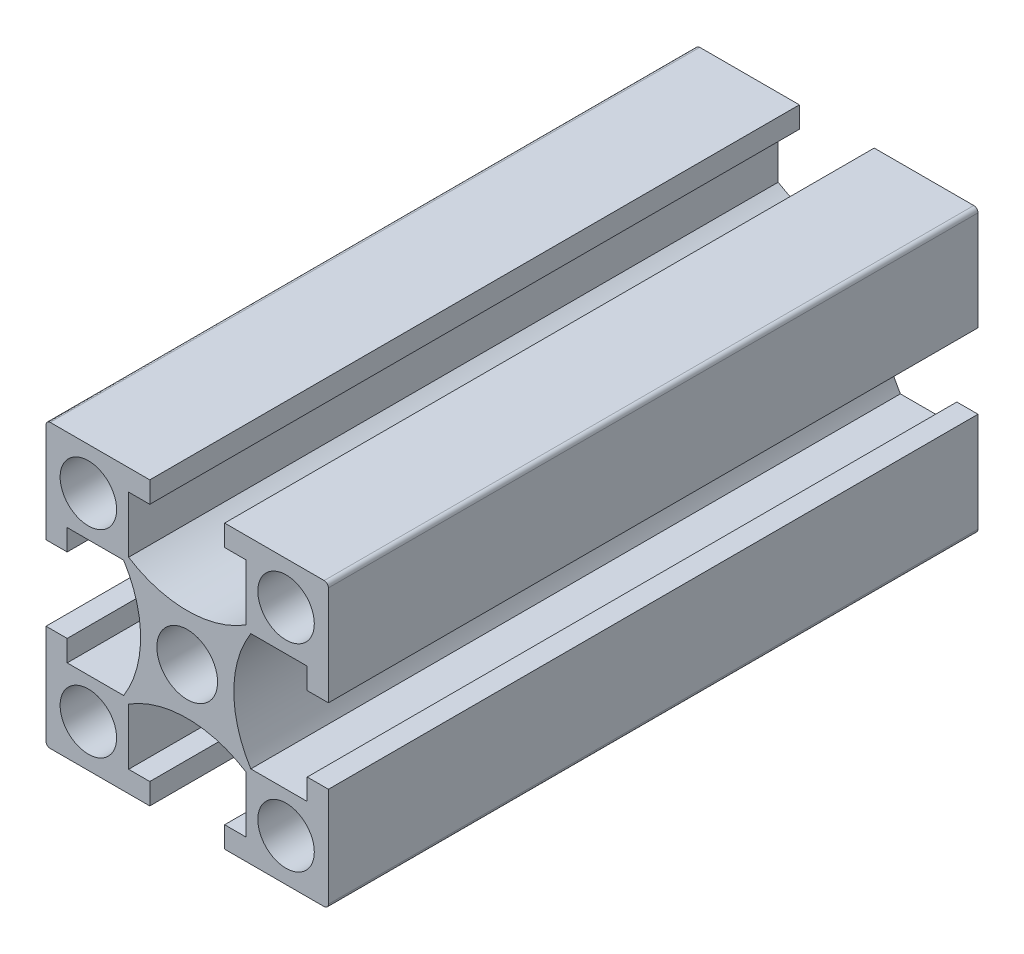
SolidWorks part; units mm, degrees
material "3.0255 (EN-AW 1350A)"
ref_plane "정면" through (0, 0, 0) normal (0, 0, 1) x (1, 0, 0)
ref_plane "윗면" through (0, 0, 0) normal (0, 1, 0) x (1, 0, 0)
ref_plane "우측면" through (0, 0, 0) normal (1, 0, 0) x (0, 0, -1)
sketch "스케치1" plane through (0, 0, 0) normal (0, 0, 1) x (1, 0, 0)
  line L0 (0, 32.0265) -> (0, -31.6588) construction
  line L1 (-10, 10) -> (-10, -10)
  line L2 (-10, 10) -> (10, 10)
  line L3 (-10, 2.65) -> (-8.5, 2.65)
  line L4 (13.6618, 0) -> (-11.6993, 0) construction
  line L5 (-8.5, 2.65) -> (-8.5, 4.15)
  line L6 (-8.5, 4.15) -> (-4.5032, 4.15)
  line L7 (-10, -2.65) -> (-8.5, -2.65)
  line L8 (-8.5, -2.65) -> (-8.5, -4.15)
  line L9 (-8.5, -4.15) -> (-4.5032, -4.15)
  line L10 (-10, -10) -> (10, -10)
  line L11 (10, 10) -> (10, -10)
  circle A0 centre (-7, 7) radius 2
  circle A1 centre (-7, -7) radius 2
  arc A2 (-4.5032, 4.15) -> (-4.5032, -4.15) centre (-11.0587, 0) cw
  circle A3 centre (0, 0) radius 2.15
  circle A4 centre (7, 7) radius 2
  circle A5 centre (7, -7) radius 2
  point P21 (-10, 0)
  point P23 (-3.3, 0)
  point P31 (0, -10)
  point P32 (0, 10)
  dimension "D3" = 4
  dimension "D9" = 6.7
  dimension "D10" = 4.3
  dimension "D11" = 7.7587
  dimension "D1" = 20
  dimension "D2" = 20
  dimension "D4" = 14
  dimension "D5" = 14
  dimension "D6" = 5.3
  dimension "D7" = 8.3
  dimension "D8" = 1.5
extrude "보스-돌출1" add sketch "스케치1" along normal blind 46 contours A0 | A4 | A3 | A5 | A1 | A2 L6 L5 L3 L1 L7 L8 L9 | L2 L11 L10 L1 region at (-6.6069, 0, 0) region at (-7, 7, 0) region at (-7, -7, 0) region at (0, 0, 0) region at (7, 7, 0) region at (7, -7, 0)
extrude "컷-돌출1" cut sketch "스케치1<3>" along normal up to next contours A2 L6 L5 L3 L1 L7 L8 L9 region at (-6.6069, 0, 0)
sketch "스케치1<3>" plane through (0, 0, 0) normal (0, 0, 1) x (1, 0, 0) same geometry as "스케치1"
pattern_circular "원형 패턴1" count 4 over 360 about axis through (0, 0, 46) along (0, 0, -1) of "컷-돌출1" reverse direction yes
fillet "필렛1" radius 0.3 4 edges at (10, -10, 23) (-10, -10, 23) (-10, 10, 23) (10, 10, 23)
sketch "스케치2" plane through (0, 0, 0) normal (1, 0, 0) x (0, 0, -1)
  line L0 (3.7612, 0) -> (-18.9549, 0) construction
  line L1 (-23, 34.3807) -> (-23, -14.9807) construction
  line L4 (0, -4.15) -> (0, 4.15) construction
  line L5 (0, 9.7) -> (-46, 9.7) construction
  line L6 (0, 9.7) -> (-46, 9.7) construction
  circle A0 centre (-8.5, 0) radius 2.5
  point P6 (-23, 9.7)
  dimension "D1" = 5
  dimension "D2" = 8.5
extrude "컷-돌출2" cut sketch "스케치2" against normal through all both and the other way through all contours A0
